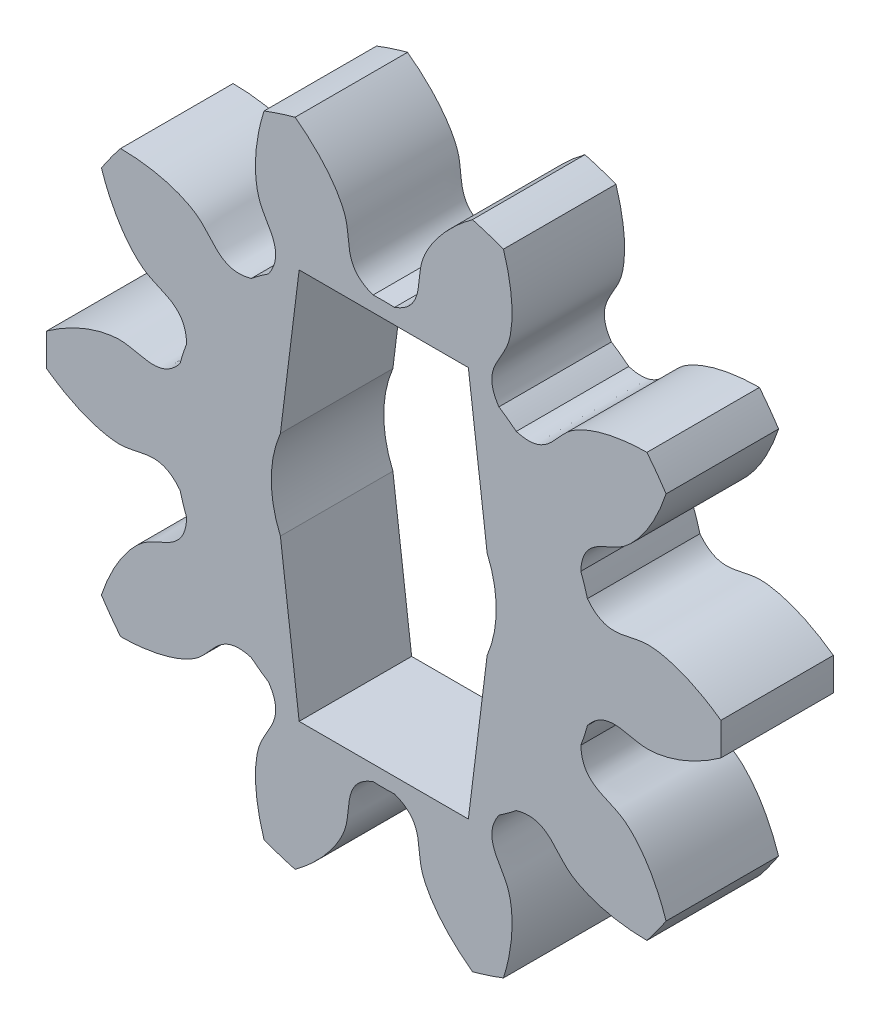
SolidWorks part; units mm, degrees
ref_plane "前视基准面" through (0, 0, 0) normal (0, 0, 1) x (1, 0, 0)
ref_plane "上视基准面" through (0, 0, 0) normal (0, 1, 0) x (1, 0, 0)
ref_plane "右视基准面" through (0, 0, 0) normal (1, 0, 0) x (0, 0, -1)
sketch "草图1" plane through (0, 0, 0) normal (0, 0, 1) x (1, 0, 0)
  circle A0 centre (0, 0) radius 12
extrude "凸台-拉伸1" add sketch "草图1" along normal blind 30
ref_axis "基准轴1" through (0, 0, 25.8) along (0, 0, 1)
sketch "草图2" plane through (0, 0, 0) normal (0, 0, 1) x (1, 0, 0)
  line L0 (0, 0) -> (0, 12) construction
  circle A0 centre (0, 0) radius 12 construction
  arc A1 (0.3809, 7.4903) -> (-0.3809, 7.4903) centre (0, 0) ccw
  arc A2 (8.5072, 13.3886) -> (-8.5072, 13.3886) centre (0, 0) ccw
  spline S0 degree 3 poles (0.3809, 7.4903) (1.4509, 7.8811) (1.1477, 8.7412) (1.3773, 9.4493) (1.389, 9.4831) (1.4027, 9.5201) (1.4184, 9.5604) (1.4364, 9.6038) (1.4568, 9.6502) (1.4797, 9.6997) (1.5052, 9.7521) (1.5335, 9.8073) (1.5646, 9.8653) (1.5987, 9.9258) (1.636, 9.989) (1.6765, 10.0545) (1.7203, 10.1225) (1.7675, 10.1926) (1.8184, 10.2648) (1.8728, 10.3391) (1.9311, 10.4152) (1.9932, 10.4931) (2.0592, 10.5726) (2.1293, 10.6537) (2.2035, 10.7361) (2.2819, 10.8197) (2.3646, 10.9045) (2.4516, 10.9902) (2.5431, 11.0768) (2.639, 11.164) (2.7395, 11.2518) (2.8447, 11.3399) (2.9545, 11.4283) (3.069, 11.5168) (3.1883, 11.6052) (3.3124, 11.6934) (3.4413, 11.7812) (3.5751, 11.8685) (3.7138, 11.9551) (3.8575, 12.0408) (4.0061, 12.1254) (4.1597, 12.2089) (4.3182, 12.291) (4.4818, 12.3716) (4.6503, 12.4505) (4.8238, 12.5275) (5.0022, 12.6025) (5.1856, 12.6753) (5.374, 12.7458) (5.5673, 12.8137) (5.7655, 12.8789) (5.9685, 12.9412) (6.1763, 13.0005) (6.389, 13.0566) (6.6063, 13.1093) (6.8284, 13.1585) (7.055, 13.2039) (7.2863, 13.2455) (7.522, 13.283) (7.7621, 13.3164) (8.0906, 13.3553) (8.3397, 13.3772) (8.5072, 13.3886) knots 0 0 0 0 0.201721 0.204697 0.208023 0.211699 0.215726 0.220102 0.224829 0.229906 0.235332 0.241109 0.247237 0.253714 0.260541 0.267719 0.275246 0.283124 0.291352 0.29993 0.308858 0.318136 0.327765 0.337743 0.348072 0.358751 0.36978 0.381158 0.392888 0.404967 0.417396 0.430176 0.443305 0.456785 0.470615 0.484795 0.499325 0.514205 0.529435 0.545016 0.560946 0.577227 0.593858 0.610839 0.62817 0.645851 0.663882 0.682264 0.700995 0.720077 0.739509 0.759291 0.779423 0.799905 0.820737 0.84192 0.863452 0.885335 0.907568 0.930151 0.953084 1 1 1 1
  spline S1 degree 3 poles (-0.3809, 7.4903) (-1.4509, 7.8811) (-1.1477, 8.7412) (-1.3773, 9.4493) (-1.389, 9.4831) (-1.4027, 9.5201) (-1.4184, 9.5604) (-1.4364, 9.6038) (-1.4568, 9.6502) (-1.4797, 9.6997) (-1.5052, 9.7521) (-1.5335, 9.8073) (-1.5646, 9.8653) (-1.5987, 9.9258) (-1.636, 9.989) (-1.6765, 10.0545) (-1.7203, 10.1225) (-1.7675, 10.1926) (-1.8184, 10.2648) (-1.8728, 10.3391) (-1.9311, 10.4152) (-1.9932, 10.4931) (-2.0592, 10.5726) (-2.1293, 10.6537) (-2.2035, 10.7361) (-2.2819, 10.8197) (-2.3646, 10.9045) (-2.4516, 10.9902) (-2.5431, 11.0768) (-2.639, 11.164) (-2.7395, 11.2518) (-2.8447, 11.3399) (-2.9545, 11.4283) (-3.069, 11.5168) (-3.1883, 11.6052) (-3.3124, 11.6934) (-3.4413, 11.7812) (-3.5751, 11.8685) (-3.7138, 11.9551) (-3.8575, 12.0408) (-4.0061, 12.1254) (-4.1597, 12.2089) (-4.3182, 12.291) (-4.4818, 12.3716) (-4.6503, 12.4505) (-4.8238, 12.5275) (-5.0022, 12.6025) (-5.1856, 12.6753) (-5.374, 12.7458) (-5.5673, 12.8137) (-5.7655, 12.8789) (-5.9685, 12.9412) (-6.1763, 13.0005) (-6.389, 13.0566) (-6.6063, 13.1093) (-6.8284, 13.1585) (-7.055, 13.2039) (-7.2863, 13.2455) (-7.522, 13.283) (-7.7621, 13.3164) (-8.0906, 13.3553) (-8.3397, 13.3772) (-8.5072, 13.3886) knots 0 0 0 0 0.201721 0.204697 0.208023 0.211699 0.215726 0.220102 0.224829 0.229906 0.235332 0.241109 0.247237 0.253714 0.260541 0.267719 0.275246 0.283124 0.291352 0.29993 0.308858 0.318136 0.327765 0.337743 0.348072 0.358751 0.36978 0.381158 0.392888 0.404967 0.417396 0.430176 0.443305 0.456785 0.470615 0.484795 0.499325 0.514205 0.529435 0.545016 0.560946 0.577227 0.593858 0.610839 0.62817 0.645851 0.663882 0.682264 0.700995 0.720077 0.739509 0.759291 0.779423 0.799905 0.820737 0.84192 0.863452 0.885335 0.907568 0.930151 0.953084 1 1 1 1
extrude "切除-拉伸1" cut sketch "草图2" along normal through all
pattern_circular "阵列(圆周)1" count 10 every 36 about axis through (0, 0, 25.8) along (0, 0, 1) of "切除-拉伸1"
sketch "草图3" plane through (0, 0, 0) normal (0, 0, 1) x (1, 0, 0)
  circle A0 centre (0, 0) radius 10 construction
  arc A21 (-4.0945, 6.2837) -> (-4.7109, 5.8359) centre (0, 0) ccw
  arc A22 (-9.3561, 7.5142) -> (-10.0376, 6.5762) centre (0, 0) ccw
  arc A23 (-7.006, 2.6769) -> (-7.2414, 1.9524) centre (0, 0) ccw
  arc A24 (-11.986, 0.5797) -> (-11.986, -0.5797) centre (0, 0) ccw
  arc A25 (-7.2414, -1.9524) -> (-7.006, -2.6769) centre (0, 0) ccw
  arc A26 (-10.0376, -6.5762) -> (-9.3561, -7.5142) centre (0, 0) ccw
  arc A27 (-4.7109, -5.8359) -> (-4.0945, -6.2837) centre (0, 0) ccw
  arc A28 (-4.2552, -11.2202) -> (-3.1525, -11.5785) centre (0, 0) ccw
  arc A29 (-0.3809, -7.4903) -> (0.3809, -7.4903) centre (0, 0) ccw
  arc A30 (3.1525, -11.5785) -> (4.2552, -11.2202) centre (0, 0) ccw
  arc A31 (4.0945, -6.2837) -> (4.7109, -5.8359) centre (0, 0) ccw
  arc A32 (9.3561, -7.5142) -> (10.0376, -6.5762) centre (0, 0) ccw
  arc A33 (7.006, -2.6769) -> (7.2414, -1.9524) centre (0, 0) ccw
  arc A34 (11.986, -0.5797) -> (11.986, 0.5797) centre (0, 0) ccw
  arc A35 (7.2414, 1.9524) -> (7.006, 2.6769) centre (0, 0) ccw
  arc A36 (10.0376, 6.5762) -> (9.3561, 7.5142) centre (0, 0) ccw
  arc A37 (4.7109, 5.8359) -> (4.0945, 6.2837) centre (0, 0) ccw
  arc A38 (4.2552, 11.2202) -> (3.1525, 11.5785) centre (0, 0) ccw
  arc A39 (0.3809, 7.4903) -> (-0.3809, 7.4903) centre (0, 0) ccw
  arc A40 (-3.1525, 11.5785) -> (-4.2552, 11.2202) centre (0, 0) ccw
  arc A41 (-4.0945, 6.2837) -> (-4.7109, 5.8359) centre (0, 0) ccw
  arc A42 (-9.3561, 7.5142) -> (-10.0376, 6.5762) centre (0, 0) ccw
  arc A43 (-7.006, 2.6769) -> (-7.2414, 1.9524) centre (0, 0) ccw
  arc A44 (-11.986, 0.5797) -> (-11.986, -0.5797) centre (0, 0) ccw
  arc A45 (-7.2414, -1.9524) -> (-7.006, -2.6769) centre (0, 0) ccw
  arc A46 (-10.0376, -6.5762) -> (-9.3561, -7.5142) centre (0, 0) ccw
  arc A47 (-4.7109, -5.8359) -> (-4.0945, -6.2837) centre (0, 0) ccw
  arc A48 (-4.2552, -11.2202) -> (-3.1525, -11.5785) centre (0, 0) ccw
  arc A49 (-0.3809, -7.4903) -> (0.3809, -7.4903) centre (0, 0) ccw
  arc A50 (3.1525, -11.5785) -> (4.2552, -11.2202) centre (0, 0) ccw
  arc A51 (4.0945, -6.2837) -> (4.7109, -5.8359) centre (0, 0) ccw
  arc A52 (9.3561, -7.5142) -> (10.0376, -6.5762) centre (0, 0) ccw
  arc A53 (7.006, -2.6769) -> (7.2414, -1.9524) centre (0, 0) ccw
  arc A54 (11.986, -0.5797) -> (11.986, 0.5797) centre (0, 0) ccw
  arc A55 (7.2414, 1.9524) -> (7.006, 2.6769) centre (0, 0) ccw
  arc A56 (10.0376, 6.5762) -> (9.3561, 7.5142) centre (0, 0) ccw
  arc A57 (4.7109, 5.8359) -> (4.0945, 6.2837) centre (0, 0) ccw
  arc A58 (4.2552, 11.2202) -> (3.1525, 11.5785) centre (0, 0) ccw
  arc A59 (0.3809, 7.4903) -> (-0.3809, 7.4903) centre (0, 0) ccw
  arc A60 (-3.1525, 11.5785) -> (-4.2552, 11.2202) centre (0, 0) ccw
  spline S20 degree 3 poles (1770.2188, 2424.0902) (-37.6526, -62.8587) (0.2169, 1.8265) (-6.6791, 6.8428) (-6.7335, 6.8799) (-6.81, 6.9276) (-6.9015, 6.9798) (-7.0083, 7.0352) (-7.1308, 7.0926) (-7.2694, 7.151) (-7.4243, 7.2091) (-7.5956, 7.2657) (-7.7836, 7.3195) (-7.9881, 7.3693) (-8.2093, 7.4139) (-8.4468, 7.452) (-8.7007, 7.4824) (-8.9705, 7.5038) (-39.116, 8.684) (-72.727, -175.0966) (2066.723, 2171.882) knots -1.637672 -1.637672 -1.637672 -1.637672 0.735149 0.738125 0.745127 0.75353 0.763333 0.774537 0.787142 0.801147 0.816552 0.833358 0.851564 0.871171 0.892178 0.914586 0.938395 0.963603 0.990213 9.367146 9.367146 9.367146 9.367146 only from (-4.7109, 5.8359) to (-9.3561, 7.5142)
  spline S21 degree 3 poles (-1410.5924, -2645.5688) (137.1352, 125.9448) (-20.9666, 32.8668) (-9.8048, 5.9626) (-9.6975, 5.7306) (-9.5878, 5.5164) (-9.4771, 5.3199) (-9.3665, 5.1408) (-9.2572, 4.9787) (-9.1505, 4.8332) (-9.0474, 4.7038) (-8.9491, 4.5901) (-8.8565, 4.4913) (-8.7709, 4.4068) (-8.693, 4.336) (-8.6239, 4.2779) (-8.5719, 4.2376) (-1.67, -0.7707) (48.1476, 55.2349) (-1758.455, -2432.7127) knots -8.052497 -8.052497 -8.052497 -8.052497 0.036397 0.061605 0.085414 0.107822 0.128829 0.148436 0.166642 0.183448 0.198853 0.212858 0.225463 0.236667 0.24647 0.254873 0.261875 0.264851 2.637688 2.637688 2.637688 2.637688 only from (-10.0376, 6.5762) to (-7.006, 2.6769)
  spline S22 degree 3 poles (7.2927, 3001.6387) (6.4858, -72.9854) (-0.8981, 1.6051) (-9.4256, 1.6101) (-9.4914, 1.6081) (-9.5814, 1.6018) (-9.686, 1.5902) (-9.805, 1.5722) (-9.9379, 1.5467) (-10.0843, 1.5125) (-10.2438, 1.4684) (-10.4157, 1.4134) (-10.5993, 1.3465) (-10.7941, 1.2666) (-10.9992, 1.1727) (-11.2138, 1.0639) (-11.437, 0.9392) (-11.6679, 0.7979) (-36.7498, -15.9663) (44.0818, -184.404) (395.4138, 2971.8787) knots -1.637672 -1.637672 -1.637672 -1.637672 0.735149 0.738125 0.745127 0.75353 0.763333 0.774537 0.787142 0.801147 0.816552 0.833358 0.851564 0.871171 0.892178 0.914586 0.938395 0.963603 0.990213 9.367146 9.367146 9.367146 9.367146 only from (-7.2414, 1.9524) to (-11.986, 0.5797)
  spline S23 degree 3 poles (413.8331, -2969.4355) (36.9162, 182.4975) (-36.2809, 14.2659) (-11.437, -0.9392) (-11.2138, -1.0639) (-10.9992, -1.1727) (-10.7941, -1.2666) (-10.5993, -1.3465) (-10.4157, -1.4134) (-10.2438, -1.4684) (-10.0843, -1.5125) (-9.9379, -1.5467) (-9.805, -1.5722) (-9.686, -1.5902) (-9.5814, -1.6018) (-9.4914, -1.6081) (-9.4256, -1.6101) (-0.8981, -1.6051) (6.4859, 72.9864) (7.2927, -3001.6998) knots -8.052497 -8.052497 -8.052497 -8.052497 0.036397 0.061605 0.085414 0.107822 0.128829 0.148436 0.166642 0.183448 0.198853 0.212858 0.225463 0.236667 0.24647 0.254873 0.261875 0.264851 2.637688 2.637688 2.637688 2.637688 only from (-11.986, -0.5797) to (-7.2414, -1.9524)
  spline S24 degree 3 poles (-1758.4191, 2432.6632) (48.1469, -55.2341) (-1.6701, 0.7707) (-8.5719, -4.2376) (-8.6239, -4.2779) (-8.693, -4.336) (-8.7709, -4.4068) (-8.8565, -4.4913) (-8.9491, -4.5901) (-9.0474, -4.7038) (-9.1505, -4.8332) (-9.2572, -4.9787) (-9.3665, -5.1408) (-9.4771, -5.3199) (-9.5878, -5.5164) (-9.6975, -5.7306) (-9.8048, -5.9626) (-9.9085, -6.2127) (-20.3465, -34.518) (144.0529, -123.2753) (-1426.93, 2636.7188) knots -1.637672 -1.637672 -1.637672 -1.637672 0.735149 0.738125 0.745127 0.75353 0.763333 0.774537 0.787142 0.801147 0.816552 0.833358 0.851564 0.871171 0.892178 0.914586 0.938395 0.963603 0.990213 9.367146 9.367146 9.367146 9.367146 only from (-7.006, -2.6769) to (-10.0376, -6.5762)
  spline S25 degree 3 poles (2080.1884, -2159.0788) (-77.4035, 169.3424) (-37.7372, -9.784) (-8.7007, -7.4824) (-8.4468, -7.452) (-8.2093, -7.4139) (-7.9881, -7.3693) (-7.7836, -7.3195) (-7.5956, -7.2657) (-7.4243, -7.2091) (-7.2694, -7.151) (-7.1308, -7.0926) (-7.0083, -7.0352) (-6.9015, -6.9798) (-6.81, -6.9277) (-6.7335, -6.8799) (-6.6791, -6.8428) (0.2169, -1.8264) (-37.6531, 62.8596) (1770.2548, -2424.1397) knots -8.052497 -8.052497 -8.052497 -8.052497 0.036397 0.061605 0.085414 0.107822 0.128829 0.148436 0.166642 0.183448 0.198853 0.212858 0.225463 0.236667 0.24647 0.254873 0.261875 0.264851 2.637688 2.637688 2.637688 2.637688 only from (-9.3561, -7.5142) to (-4.7109, -5.8359)
  spline S26 degree 3 poles (-2852.4745, 934.4931) (71.4175, -16.3853) (-1.8041, -0.3581) (-4.444, -8.4668) (-4.4624, -8.5299) (-4.4842, -8.6175) (-4.5055, -8.7206) (-4.5252, -8.8393) (-4.542, -8.9735) (-4.5547, -9.1234) (-4.562, -9.2886) (-4.5629, -9.4691) (-4.556, -9.6645) (-4.5402, -9.8744) (-4.5142, -10.0985) (-4.4771, -10.3362) (-4.4275, -10.587) (-4.3645, -10.8503) (3.8285, -39.885) (189.0006, -15.0597) (-2704.2351, 1294.4219) knots -1.637672 -1.637672 -1.637672 -1.637672 0.735149 0.738125 0.745127 0.75353 0.763333 0.774537 0.787142 0.801147 0.816552 0.833358 0.851564 0.871171 0.892178 0.914586 0.938395 0.963603 0.990213 9.367146 9.367146 9.367146 9.367146 only from (-4.0945, -6.2837) to (-4.2552, -11.2202)
  spline S27 degree 3 poles (2951.9824, -524.0274) (-162.1577, 91.5042) (-24.7791, -30.0968) (-2.641, -11.1675) (-2.4534, -10.9937) (-2.2836, -10.8233) (-2.131, -10.6572) (-1.9948, -10.4967) (-1.8744, -10.3427) (-1.769, -10.1962) (-1.6778, -10.0581) (-1.6, -9.9295) (-1.5346, -9.8109) (-1.4808, -9.7034) (-1.4375, -9.6074) (-1.4036, -9.5238) (-1.3814, -9.4619) (1.249, -1.3501) (-67.4099, 28.7225) (2857.0398, -920.6405) knots -8.052497 -8.052497 -8.052497 -8.052497 0.036397 0.061605 0.085414 0.107822 0.128829 0.148436 0.166642 0.183448 0.198853 0.212858 0.225463 0.236667 0.24647 0.254873 0.261875 0.264851 2.637688 2.637688 2.637688 2.637688 only from (-3.1525, -11.5785) to (-0.3809, -7.4903)
  spline S28 degree 3 poles (-2856.9816, -920.6216) (67.409, 28.7221) (-1.249, -1.3502) (1.3814, -9.4619) (1.4036, -9.5238) (1.4375, -9.6074) (1.4808, -9.7034) (1.5346, -9.8109) (1.6, -9.9295) (1.6778, -10.0581) (1.769, -10.1962) (1.8744, -10.3427) (1.9948, -10.4967) (2.131, -10.6572) (2.2836, -10.8233) (2.4534, -10.9937) (2.641, -11.1675) (2.8467, -11.3434) (26.5412, -30.0173) (161.7566, 98.9083) (-2948.6142, -542.3002) knots -1.637672 -1.637672 -1.637672 -1.637672 0.735149 0.738125 0.745127 0.75353 0.763333 0.774537 0.787142 0.801147 0.816552 0.833358 0.851564 0.871171 0.892178 0.914586 0.938395 0.963603 0.990213 9.367146 9.367146 9.367146 9.367146 only from (0.3809, -7.4903) to (3.1525, -11.5785)
  spline S29 degree 3 poles (2696.2195, 1311.1847) (-184.9732, -21.2855) (-2.3563, -38.9136) (4.4275, -10.587) (4.4771, -10.3362) (4.5142, -10.0985) (4.5402, -9.8744) (4.556, -9.6645) (4.5629, -9.4691) (4.562, -9.2886) (4.5547, -9.1234) (4.542, -8.9735) (4.5252, -8.8393) (4.5055, -8.7206) (4.4842, -8.6175) (4.4624, -8.5299) (4.444, -8.4668) (1.8041, -0.3581) (-71.4184, -16.3855) (2852.5326, 934.512) knots -8.052497 -8.052497 -8.052497 -8.052497 0.036397 0.061605 0.085414 0.107822 0.128829 0.148436 0.166642 0.183448 0.198853 0.212858 0.225463 0.236667 0.24647 0.254873 0.261875 0.264851 2.637688 2.637688 2.637688 2.637688 only from (4.2552, -11.2202) to (4.0945, -6.2837)
  spline S30 degree 3 poles (-1770.2188, -2424.0902) (37.6526, 62.8587) (-0.2169, -1.8265) (6.6791, -6.8428) (6.7335, -6.8799) (6.81, -6.9276) (6.9015, -6.9798) (7.0083, -7.0352) (7.1308, -7.0926) (7.2694, -7.151) (7.4243, -7.2091) (7.5956, -7.2657) (7.7836, -7.3195) (7.9881, -7.3693) (8.2093, -7.4139) (8.4468, -7.452) (8.7007, -7.4824) (8.9705, -7.5038) (39.116, -8.684) (72.727, 175.0966) (-2066.723, -2171.882) knots -1.637672 -1.637672 -1.637672 -1.637672 0.735149 0.738125 0.745127 0.75353 0.763333 0.774537 0.787142 0.801147 0.816552 0.833358 0.851564 0.871171 0.892178 0.914586 0.938395 0.963603 0.990213 9.367146 9.367146 9.367146 9.367146 only from (4.7109, -5.8359) to (9.3561, -7.5142)
  spline S31 degree 3 poles (1410.5924, 2645.5688) (-137.1352, -125.9448) (20.9666, -32.8668) (9.8048, -5.9626) (9.6975, -5.7306) (9.5878, -5.5164) (9.4771, -5.3199) (9.3665, -5.1408) (9.2572, -4.9787) (9.1505, -4.8332) (9.0474, -4.7038) (8.9491, -4.5901) (8.8565, -4.4913) (8.7709, -4.4068) (8.693, -4.336) (8.6239, -4.2779) (8.5719, -4.2376) (1.67, 0.7707) (-48.1476, -55.2349) (1758.455, 2432.7127) knots -8.052497 -8.052497 -8.052497 -8.052497 0.036397 0.061605 0.085414 0.107822 0.128829 0.148436 0.166642 0.183448 0.198853 0.212858 0.225463 0.236667 0.24647 0.254873 0.261875 0.264851 2.637688 2.637688 2.637688 2.637688 only from (10.0376, -6.5762) to (7.006, -2.6769)
  spline S32 degree 3 poles (-7.2927, -3001.6387) (-6.4858, 72.9854) (0.8981, -1.6051) (9.4256, -1.6101) (9.4914, -1.6081) (9.5814, -1.6018) (9.686, -1.5902) (9.805, -1.5722) (9.9379, -1.5467) (10.0843, -1.5125) (10.2438, -1.4684) (10.4157, -1.4134) (10.5993, -1.3465) (10.7941, -1.2666) (10.9992, -1.1727) (11.2138, -1.0639) (11.437, -0.9392) (11.6679, -0.7979) (36.7498, 15.9663) (-44.0818, 184.404) (-395.4138, -2971.8787) knots -1.637672 -1.637672 -1.637672 -1.637672 0.735149 0.738125 0.745127 0.75353 0.763333 0.774537 0.787142 0.801147 0.816552 0.833358 0.851564 0.871171 0.892178 0.914586 0.938395 0.963603 0.990213 9.367146 9.367146 9.367146 9.367146 only from (7.2414, -1.9524) to (11.986, -0.5797)
  spline S33 degree 3 poles (-413.8331, 2969.4355) (-36.9162, -182.4975) (36.2809, -14.2659) (11.437, 0.9392) (11.2138, 1.0639) (10.9992, 1.1727) (10.7941, 1.2666) (10.5993, 1.3465) (10.4157, 1.4134) (10.2438, 1.4684) (10.0843, 1.5125) (9.9379, 1.5467) (9.805, 1.5722) (9.686, 1.5902) (9.5814, 1.6018) (9.4914, 1.6081) (9.4256, 1.6101) (0.8981, 1.6051) (-6.4859, -72.9864) (-7.2927, 3001.6998) knots -8.052497 -8.052497 -8.052497 -8.052497 0.036397 0.061605 0.085414 0.107822 0.128829 0.148436 0.166642 0.183448 0.198853 0.212858 0.225463 0.236667 0.24647 0.254873 0.261875 0.264851 2.637688 2.637688 2.637688 2.637688 only from (11.986, 0.5797) to (7.2414, 1.9524)
  spline S34 degree 3 poles (1758.4191, -2432.6632) (-48.1469, 55.2341) (1.6701, -0.7707) (8.5719, 4.2376) (8.6239, 4.2779) (8.693, 4.336) (8.7709, 4.4068) (8.8565, 4.4913) (8.9491, 4.5901) (9.0474, 4.7038) (9.1505, 4.8332) (9.2572, 4.9787) (9.3665, 5.1408) (9.4771, 5.3199) (9.5878, 5.5164) (9.6975, 5.7306) (9.8048, 5.9626) (9.9085, 6.2127) (20.3465, 34.518) (-144.0529, 123.2753) (1426.93, -2636.7188) knots -1.637672 -1.637672 -1.637672 -1.637672 0.735149 0.738125 0.745127 0.75353 0.763333 0.774537 0.787142 0.801147 0.816552 0.833358 0.851564 0.871171 0.892178 0.914586 0.938395 0.963603 0.990213 9.367146 9.367146 9.367146 9.367146 only from (7.006, 2.6769) to (10.0376, 6.5762)
  spline S35 degree 3 poles (-2080.1884, 2159.0788) (77.4035, -169.3424) (37.7372, 9.784) (8.7007, 7.4824) (8.4468, 7.452) (8.2093, 7.4139) (7.9881, 7.3693) (7.7836, 7.3195) (7.5956, 7.2657) (7.4243, 7.2091) (7.2694, 7.151) (7.1308, 7.0926) (7.0083, 7.0352) (6.9015, 6.9798) (6.81, 6.9277) (6.7335, 6.8799) (6.6791, 6.8428) (-0.2169, 1.8264) (37.6531, -62.8596) (-1770.2548, 2424.1397) knots -8.052497 -8.052497 -8.052497 -8.052497 0.036397 0.061605 0.085414 0.107822 0.128829 0.148436 0.166642 0.183448 0.198853 0.212858 0.225463 0.236667 0.24647 0.254873 0.261875 0.264851 2.637688 2.637688 2.637688 2.637688 only from (9.3561, 7.5142) to (4.7109, 5.8359)
  spline S36 degree 3 poles (2852.4745, -934.4931) (-71.4175, 16.3853) (1.8041, 0.3581) (4.444, 8.4668) (4.4624, 8.5299) (4.4842, 8.6175) (4.5055, 8.7206) (4.5252, 8.8393) (4.542, 8.9735) (4.5547, 9.1234) (4.562, 9.2886) (4.5629, 9.4691) (4.556, 9.6645) (4.5402, 9.8744) (4.5142, 10.0985) (4.4771, 10.3362) (4.4275, 10.587) (4.3645, 10.8503) (-3.8285, 39.885) (-189.0006, 15.0597) (2704.2351, -1294.4219) knots -1.637672 -1.637672 -1.637672 -1.637672 0.735149 0.738125 0.745127 0.75353 0.763333 0.774537 0.787142 0.801147 0.816552 0.833358 0.851564 0.871171 0.892178 0.914586 0.938395 0.963603 0.990213 9.367146 9.367146 9.367146 9.367146 only from (4.0945, 6.2837) to (4.2552, 11.2202)
  spline S37 degree 3 poles (-2951.9824, 524.0274) (162.1577, -91.5042) (24.7791, 30.0968) (2.641, 11.1675) (2.4534, 10.9937) (2.2836, 10.8233) (2.131, 10.6572) (1.9948, 10.4967) (1.8744, 10.3427) (1.769, 10.1962) (1.6778, 10.0581) (1.6, 9.9295) (1.5346, 9.8109) (1.4808, 9.7034) (1.4375, 9.6074) (1.4036, 9.5238) (1.3814, 9.4619) (-1.249, 1.3501) (67.4099, -28.7225) (-2857.0398, 920.6405) knots -8.052497 -8.052497 -8.052497 -8.052497 0.036397 0.061605 0.085414 0.107822 0.128829 0.148436 0.166642 0.183448 0.198853 0.212858 0.225463 0.236667 0.24647 0.254873 0.261875 0.264851 2.637688 2.637688 2.637688 2.637688 only from (3.1525, 11.5785) to (0.3809, 7.4903)
  spline S38 degree 3 poles (2856.9816, 920.6216) (-67.409, -28.7221) (1.249, 1.3502) (-1.3814, 9.4619) (-1.4036, 9.5238) (-1.4375, 9.6074) (-1.4808, 9.7034) (-1.5346, 9.8109) (-1.6, 9.9295) (-1.6778, 10.0581) (-1.769, 10.1962) (-1.8744, 10.3427) (-1.9948, 10.4967) (-2.131, 10.6572) (-2.2836, 10.8233) (-2.4534, 10.9937) (-2.641, 11.1675) (-2.8467, 11.3434) (-26.5412, 30.0173) (-161.7566, -98.9083) (2948.6142, 542.3002) knots -1.637672 -1.637672 -1.637672 -1.637672 0.735149 0.738125 0.745127 0.75353 0.763333 0.774537 0.787142 0.801147 0.816552 0.833358 0.851564 0.871171 0.892178 0.914586 0.938395 0.963603 0.990213 9.367146 9.367146 9.367146 9.367146 only from (-0.3809, 7.4903) to (-3.1525, 11.5785)
  spline S39 degree 3 poles (-2696.2195, -1311.1847) (184.9732, 21.2855) (2.3563, 38.9136) (-4.4275, 10.587) (-4.4771, 10.3362) (-4.5142, 10.0985) (-4.5402, 9.8744) (-4.556, 9.6645) (-4.5629, 9.4691) (-4.562, 9.2886) (-4.5547, 9.1234) (-4.542, 8.9735) (-4.5252, 8.8393) (-4.5055, 8.7206) (-4.4842, 8.6175) (-4.4624, 8.5299) (-4.444, 8.4668) (-1.8041, 0.3581) (71.4184, 16.3855) (-2852.5326, -934.512) knots -8.052497 -8.052497 -8.052497 -8.052497 0.036397 0.061605 0.085414 0.107822 0.128829 0.148436 0.166642 0.183448 0.198853 0.212858 0.225463 0.236667 0.24647 0.254873 0.261875 0.264851 2.637688 2.637688 2.637688 2.637688 only from (-4.2552, 11.2202) to (-4.0945, 6.2837)
  spline S40 degree 3 poles (-4.7109, 5.8359) (-5.8062, 5.5232) (-6.0664, 6.3972) (-6.6791, 6.8428) (-6.7335, 6.8799) (-6.81, 6.9276) (-6.9015, 6.9798) (-7.0083, 7.0352) (-7.1308, 7.0926) (-7.2694, 7.151) (-7.4243, 7.2091) (-7.5956, 7.2657) (-7.7836, 7.3195) (-7.9881, 7.3693) (-8.2093, 7.4139) (-8.4468, 7.452) (-8.7007, 7.4824) (-8.9705, 7.5038) (-9.1908, 7.5124) (-9.3211, 7.514) (-9.3561, 7.5142) knots 0.533428 0.533428 0.533428 0.533428 0.735149 0.738125 0.745127 0.75353 0.763333 0.774537 0.787142 0.801147 0.816552 0.833358 0.851564 0.871171 0.892178 0.914586 0.938395 0.963603 0.990213 1 1 1 1
  spline S41 degree 3 poles (-10.0376, 6.5762) (-9.9967, 6.4525) (-9.922, 6.245) (-9.8048, 5.9626) (-9.6975, 5.7306) (-9.5878, 5.5164) (-9.4771, 5.3199) (-9.3665, 5.1408) (-9.2572, 4.9787) (-9.1505, 4.8332) (-9.0474, 4.7038) (-8.9491, 4.5901) (-8.8565, 4.4913) (-8.7709, 4.4068) (-8.693, 4.336) (-8.6239, 4.2779) (-8.5719, 4.2376) (-7.9587, 3.7927) (-7.0471, 3.8153) (-7.006, 2.6769) knots 0 0 0 0 0.036397 0.061605 0.085414 0.107822 0.128829 0.148436 0.166642 0.183448 0.198853 0.212858 0.225463 0.236667 0.24647 0.254873 0.261875 0.264851 0.466572 0.466572 0.466572 0.466572
  spline S42 degree 3 poles (-7.2414, 1.9524) (-7.9437, 1.0556) (-8.668, 1.6097) (-9.4256, 1.6101) (-9.4914, 1.6081) (-9.5814, 1.6018) (-9.686, 1.5902) (-9.805, 1.5722) (-9.9379, 1.5467) (-10.0843, 1.5125) (-10.2438, 1.4684) (-10.4157, 1.4134) (-10.5993, 1.3465) (-10.7941, 1.2666) (-10.9992, 1.1727) (-11.2138, 1.0639) (-11.437, 0.9392) (-11.6679, 0.7979) (-11.8512, 0.6754) (-11.9575, 0.6002) (-11.986, 0.5797) knots 0.533428 0.533428 0.533428 0.533428 0.735149 0.738125 0.745127 0.75353 0.763333 0.774537 0.787142 0.801147 0.816552 0.833358 0.851564 0.871171 0.892178 0.914586 0.938395 0.963603 0.990213 1 1 1 1
  spline S43 degree 3 poles (-11.986, -0.5797) (-11.8802, -0.6557) (-11.6978, -0.7797) (-11.437, -0.9392) (-11.2138, -1.0639) (-10.9992, -1.1727) (-10.7941, -1.2666) (-10.5993, -1.3465) (-10.4157, -1.4134) (-10.2438, -1.4684) (-10.0843, -1.5125) (-9.9379, -1.5467) (-9.805, -1.5722) (-9.686, -1.5902) (-9.5814, -1.6018) (-9.4914, -1.6081) (-9.4256, -1.6101) (-8.668, -1.6097) (-7.9437, -1.0556) (-7.2414, -1.9524) knots 0 0 0 0 0.036397 0.061605 0.085414 0.107822 0.128829 0.148436 0.166642 0.183448 0.198853 0.212858 0.225463 0.236667 0.24647 0.254873 0.261875 0.264851 0.466572 0.466572 0.466572 0.466572
  spline S44 degree 3 poles (-7.006, -2.6769) (-7.0471, -3.8153) (-7.9587, -3.7927) (-8.5719, -4.2376) (-8.6239, -4.2779) (-8.693, -4.336) (-8.7709, -4.4068) (-8.8565, -4.4913) (-8.9491, -4.5901) (-9.0474, -4.7038) (-9.1505, -4.8332) (-9.2572, -4.9787) (-9.3665, -5.1408) (-9.4771, -5.3199) (-9.5878, -5.5164) (-9.6975, -5.7306) (-9.8048, -5.9626) (-9.9085, -6.2127) (-9.9848, -6.4196) (-10.0266, -6.5429) (-10.0376, -6.5762) knots 0.533428 0.533428 0.533428 0.533428 0.735149 0.738125 0.745127 0.75353 0.763333 0.774537 0.787142 0.801147 0.816552 0.833358 0.851564 0.871171 0.892178 0.914586 0.938395 0.963603 0.990213 1 1 1 1
  spline S45 degree 3 poles (-9.3561, -7.5142) (-9.2259, -7.5135) (-9.0054, -7.5065) (-8.7007, -7.4824) (-8.4468, -7.452) (-8.2093, -7.4139) (-7.9881, -7.3693) (-7.7836, -7.3195) (-7.5956, -7.2657) (-7.4243, -7.2091) (-7.2694, -7.151) (-7.1308, -7.0926) (-7.0083, -7.0352) (-6.9015, -6.9798) (-6.81, -6.9277) (-6.7335, -6.8799) (-6.6791, -6.8428) (-6.0664, -6.3972) (-5.8062, -5.5232) (-4.7109, -5.8359) knots 0 0 0 0 0.036397 0.061605 0.085414 0.107822 0.128829 0.148436 0.166642 0.183448 0.198853 0.212858 0.225463 0.236667 0.24647 0.254873 0.261875 0.264851 0.466572 0.466572 0.466572 0.466572
  spline S46 degree 3 poles (-4.0945, -6.2837) (-3.4586, -7.2288) (-4.2094, -7.7464) (-4.444, -8.4668) (-4.4624, -8.5299) (-4.4842, -8.6175) (-4.5055, -8.7206) (-4.5252, -8.8393) (-4.542, -8.9735) (-4.5547, -9.1234) (-4.562, -9.2886) (-4.5629, -9.4691) (-4.556, -9.6645) (-4.5402, -9.8744) (-4.5142, -10.0985) (-4.4771, -10.3362) (-4.4275, -10.587) (-4.3645, -10.8503) (-4.3046, -11.0625) (-4.2659, -11.1868) (-4.2552, -11.2202) knots 0.533428 0.533428 0.533428 0.533428 0.735149 0.738125 0.745127 0.75353 0.763333 0.774537 0.787142 0.801147 0.816552 0.833358 0.851564 0.871171 0.892178 0.914586 0.938395 0.963603 0.990213 1 1 1 1
  spline S47 degree 3 poles (-3.1525, -11.5785) (-3.0476, -11.5014) (-2.8733, -11.3662) (-2.641, -11.1675) (-2.4534, -10.9937) (-2.2836, -10.8233) (-2.131, -10.6572) (-1.9948, -10.4967) (-1.8744, -10.3427) (-1.769, -10.1962) (-1.6778, -10.0581) (-1.6, -9.9295) (-1.5346, -9.8109) (-1.4808, -9.7034) (-1.4375, -9.6074) (-1.4036, -9.5238) (-1.3814, -9.4619) (-1.1477, -8.7412) (-1.4509, -7.8811) (-0.3809, -7.4903) knots 0 0 0 0 0.036397 0.061605 0.085414 0.107822 0.128829 0.148436 0.166642 0.183448 0.198853 0.212858 0.225463 0.236667 0.24647 0.254873 0.261875 0.264851 0.466572 0.466572 0.466572 0.466572
  spline S48 degree 3 poles (0.3809, -7.4903) (1.4509, -7.8811) (1.1477, -8.7412) (1.3814, -9.4619) (1.4036, -9.5238) (1.4375, -9.6074) (1.4808, -9.7034) (1.5346, -9.8109) (1.6, -9.9295) (1.6778, -10.0581) (1.769, -10.1962) (1.8744, -10.3427) (1.9948, -10.4967) (2.131, -10.6572) (2.2836, -10.8233) (2.4534, -10.9937) (2.641, -11.1675) (2.8467, -11.3434) (3.0199, -11.4799) (3.1243, -11.5578) (3.1525, -11.5785) knots 0.533428 0.533428 0.533428 0.533428 0.735149 0.738125 0.745127 0.75353 0.763333 0.774537 0.787142 0.801147 0.816552 0.833358 0.851564 0.871171 0.892178 0.914586 0.938395 0.963603 0.990213 1 1 1 1
  spline S49 degree 3 poles (4.2552, -11.2202) (4.2948, -11.0961) (4.3563, -10.8843) (4.4275, -10.587) (4.4771, -10.3362) (4.5142, -10.0985) (4.5402, -9.8744) (4.556, -9.6645) (4.5629, -9.4691) (4.562, -9.2886) (4.5547, -9.1234) (4.542, -8.9735) (4.5252, -8.8393) (4.5055, -8.7206) (4.4842, -8.6175) (4.4624, -8.5299) (4.444, -8.4668) (4.2094, -7.7464) (3.4586, -7.2288) (4.0945, -6.2837) knots 0 0 0 0 0.036397 0.061605 0.085414 0.107822 0.128829 0.148436 0.166642 0.183448 0.198853 0.212858 0.225463 0.236667 0.24647 0.254873 0.261875 0.264851 0.466572 0.466572 0.466572 0.466572
  spline S50 degree 3 poles (4.7109, -5.8359) (5.8062, -5.5232) (6.0664, -6.3972) (6.6791, -6.8428) (6.7335, -6.8799) (6.81, -6.9276) (6.9015, -6.9798) (7.0083, -7.0352) (7.1308, -7.0926) (7.2694, -7.151) (7.4243, -7.2091) (7.5956, -7.2657) (7.7836, -7.3195) (7.9881, -7.3693) (8.2093, -7.4139) (8.4468, -7.452) (8.7007, -7.4824) (8.9705, -7.5038) (9.1908, -7.5124) (9.3211, -7.514) (9.3561, -7.5142) knots 0.533428 0.533428 0.533428 0.533428 0.735149 0.738125 0.745127 0.75353 0.763333 0.774537 0.787142 0.801147 0.816552 0.833358 0.851564 0.871171 0.892178 0.914586 0.938395 0.963603 0.990213 1 1 1 1
  spline S51 degree 3 poles (10.0376, -6.5762) (9.9967, -6.4525) (9.922, -6.245) (9.8048, -5.9626) (9.6975, -5.7306) (9.5878, -5.5164) (9.4771, -5.3199) (9.3665, -5.1408) (9.2572, -4.9787) (9.1505, -4.8332) (9.0474, -4.7038) (8.9491, -4.5901) (8.8565, -4.4913) (8.7709, -4.4068) (8.693, -4.336) (8.6239, -4.2779) (8.5719, -4.2376) (7.9587, -3.7927) (7.0471, -3.8153) (7.006, -2.6769) knots 0 0 0 0 0.036397 0.061605 0.085414 0.107822 0.128829 0.148436 0.166642 0.183448 0.198853 0.212858 0.225463 0.236667 0.24647 0.254873 0.261875 0.264851 0.466572 0.466572 0.466572 0.466572
  spline S52 degree 3 poles (7.2414, -1.9524) (7.9437, -1.0556) (8.668, -1.6097) (9.4256, -1.6101) (9.4914, -1.6081) (9.5814, -1.6018) (9.686, -1.5902) (9.805, -1.5722) (9.9379, -1.5467) (10.0843, -1.5125) (10.2438, -1.4684) (10.4157, -1.4134) (10.5993, -1.3465) (10.7941, -1.2666) (10.9992, -1.1727) (11.2138, -1.0639) (11.437, -0.9392) (11.6679, -0.7979) (11.8512, -0.6754) (11.9575, -0.6002) (11.986, -0.5797) knots 0.533428 0.533428 0.533428 0.533428 0.735149 0.738125 0.745127 0.75353 0.763333 0.774537 0.787142 0.801147 0.816552 0.833358 0.851564 0.871171 0.892178 0.914586 0.938395 0.963603 0.990213 1 1 1 1
  spline S53 degree 3 poles (11.986, 0.5797) (11.8802, 0.6557) (11.6978, 0.7797) (11.437, 0.9392) (11.2138, 1.0639) (10.9992, 1.1727) (10.7941, 1.2666) (10.5993, 1.3465) (10.4157, 1.4134) (10.2438, 1.4684) (10.0843, 1.5125) (9.9379, 1.5467) (9.805, 1.5722) (9.686, 1.5902) (9.5814, 1.6018) (9.4914, 1.6081) (9.4256, 1.6101) (8.668, 1.6097) (7.9437, 1.0556) (7.2414, 1.9524) knots 0 0 0 0 0.036397 0.061605 0.085414 0.107822 0.128829 0.148436 0.166642 0.183448 0.198853 0.212858 0.225463 0.236667 0.24647 0.254873 0.261875 0.264851 0.466572 0.466572 0.466572 0.466572
  spline S54 degree 3 poles (7.006, 2.6769) (7.0471, 3.8153) (7.9587, 3.7927) (8.5719, 4.2376) (8.6239, 4.2779) (8.693, 4.336) (8.7709, 4.4068) (8.8565, 4.4913) (8.9491, 4.5901) (9.0474, 4.7038) (9.1505, 4.8332) (9.2572, 4.9787) (9.3665, 5.1408) (9.4771, 5.3199) (9.5878, 5.5164) (9.6975, 5.7306) (9.8048, 5.9626) (9.9085, 6.2127) (9.9848, 6.4196) (10.0266, 6.5429) (10.0376, 6.5762) knots 0.533428 0.533428 0.533428 0.533428 0.735149 0.738125 0.745127 0.75353 0.763333 0.774537 0.787142 0.801147 0.816552 0.833358 0.851564 0.871171 0.892178 0.914586 0.938395 0.963603 0.990213 1 1 1 1
  spline S55 degree 3 poles (9.3561, 7.5142) (9.2259, 7.5135) (9.0054, 7.5065) (8.7007, 7.4824) (8.4468, 7.452) (8.2093, 7.4139) (7.9881, 7.3693) (7.7836, 7.3195) (7.5956, 7.2657) (7.4243, 7.2091) (7.2694, 7.151) (7.1308, 7.0926) (7.0083, 7.0352) (6.9015, 6.9798) (6.81, 6.9277) (6.7335, 6.8799) (6.6791, 6.8428) (6.0664, 6.3972) (5.8062, 5.5232) (4.7109, 5.8359) knots 0 0 0 0 0.036397 0.061605 0.085414 0.107822 0.128829 0.148436 0.166642 0.183448 0.198853 0.212858 0.225463 0.236667 0.24647 0.254873 0.261875 0.264851 0.466572 0.466572 0.466572 0.466572
  spline S56 degree 3 poles (4.0945, 6.2837) (3.4586, 7.2288) (4.2094, 7.7464) (4.444, 8.4668) (4.4624, 8.5299) (4.4842, 8.6175) (4.5055, 8.7206) (4.5252, 8.8393) (4.542, 8.9735) (4.5547, 9.1234) (4.562, 9.2886) (4.5629, 9.4691) (4.556, 9.6645) (4.5402, 9.8744) (4.5142, 10.0985) (4.4771, 10.3362) (4.4275, 10.587) (4.3645, 10.8503) (4.3046, 11.0625) (4.2659, 11.1868) (4.2552, 11.2202) knots 0.533428 0.533428 0.533428 0.533428 0.735149 0.738125 0.745127 0.75353 0.763333 0.774537 0.787142 0.801147 0.816552 0.833358 0.851564 0.871171 0.892178 0.914586 0.938395 0.963603 0.990213 1 1 1 1
  spline S57 degree 3 poles (3.1525, 11.5785) (3.0476, 11.5014) (2.8733, 11.3662) (2.641, 11.1675) (2.4534, 10.9937) (2.2836, 10.8233) (2.131, 10.6572) (1.9948, 10.4967) (1.8744, 10.3427) (1.769, 10.1962) (1.6778, 10.0581) (1.6, 9.9295) (1.5346, 9.8109) (1.4808, 9.7034) (1.4375, 9.6074) (1.4036, 9.5238) (1.3814, 9.4619) (1.1477, 8.7412) (1.4509, 7.8811) (0.3809, 7.4903) knots 0 0 0 0 0.036397 0.061605 0.085414 0.107822 0.128829 0.148436 0.166642 0.183448 0.198853 0.212858 0.225463 0.236667 0.24647 0.254873 0.261875 0.264851 0.466572 0.466572 0.466572 0.466572
  spline S58 degree 3 poles (-0.3809, 7.4903) (-1.4509, 7.8811) (-1.1477, 8.7412) (-1.3814, 9.4619) (-1.4036, 9.5238) (-1.4375, 9.6074) (-1.4808, 9.7034) (-1.5346, 9.8109) (-1.6, 9.9295) (-1.6778, 10.0581) (-1.769, 10.1962) (-1.8744, 10.3427) (-1.9948, 10.4967) (-2.131, 10.6572) (-2.2836, 10.8233) (-2.4534, 10.9937) (-2.641, 11.1675) (-2.8467, 11.3434) (-3.0199, 11.4799) (-3.1243, 11.5578) (-3.1525, 11.5785) knots 0.533428 0.533428 0.533428 0.533428 0.735149 0.738125 0.745127 0.75353 0.763333 0.774537 0.787142 0.801147 0.816552 0.833358 0.851564 0.871171 0.892178 0.914586 0.938395 0.963603 0.990213 1 1 1 1
  spline S59 degree 3 poles (-4.2552, 11.2202) (-4.2948, 11.0961) (-4.3563, 10.8843) (-4.4275, 10.587) (-4.4771, 10.3362) (-4.5142, 10.0985) (-4.5402, 9.8744) (-4.556, 9.6645) (-4.5629, 9.4691) (-4.562, 9.2886) (-4.5547, 9.1234) (-4.542, 8.9735) (-4.5252, 8.8393) (-4.5055, 8.7206) (-4.4842, 8.6175) (-4.4624, 8.5299) (-4.444, 8.4668) (-4.2094, 7.7464) (-3.4586, 7.2288) (-4.0945, 6.2837) knots 0 0 0 0 0.036397 0.061605 0.085414 0.107822 0.128829 0.148436 0.166642 0.183448 0.198853 0.212858 0.225463 0.236667 0.24647 0.254873 0.261875 0.264851 0.466572 0.466572 0.466572 0.466572
  dimension "Dn" = 20
  dimension "D1" = 0
extrude "切除-拉伸2" cut sketch "草图3" along normal blind 26
sketch "草图4" plane through (0, 0, 26) normal (0, 0, -1) x (-1, 0, 0)
  line L0 (-3.0081, 6.9501) -> (3.0081, 6.9501)
  line L3 (0, -1000) -> (0, 49000) construction
  line L4 (-1000, 0) -> (49000, 0) construction
  line L6 (-3.6748, 1.5798) -> (-3.0081, 6.9501)
  line L7 (3.6748, 1.5798) -> (3.0081, 6.9501)
  line L12 (-3.6748, -1.5798) -> (-3.0081, -6.9501)
  line L13 (-3.0081, -6.9501) -> (3.0081, -6.9501)
  line L14 (3.6748, -1.5798) -> (3.0081, -6.9501)
  arc A0 (-3.6748, 1.5798) -> (-3.6748, -1.5798) centre (0, 0) ccw
  arc A1 (3.6748, -1.5798) -> (3.6748, 1.5798) centre (0, 0) ccw
  point P0 (0, 0)
  dimension "D1" = 8
extrude "切除-拉伸3" cut sketch "草图4" against normal up to next
